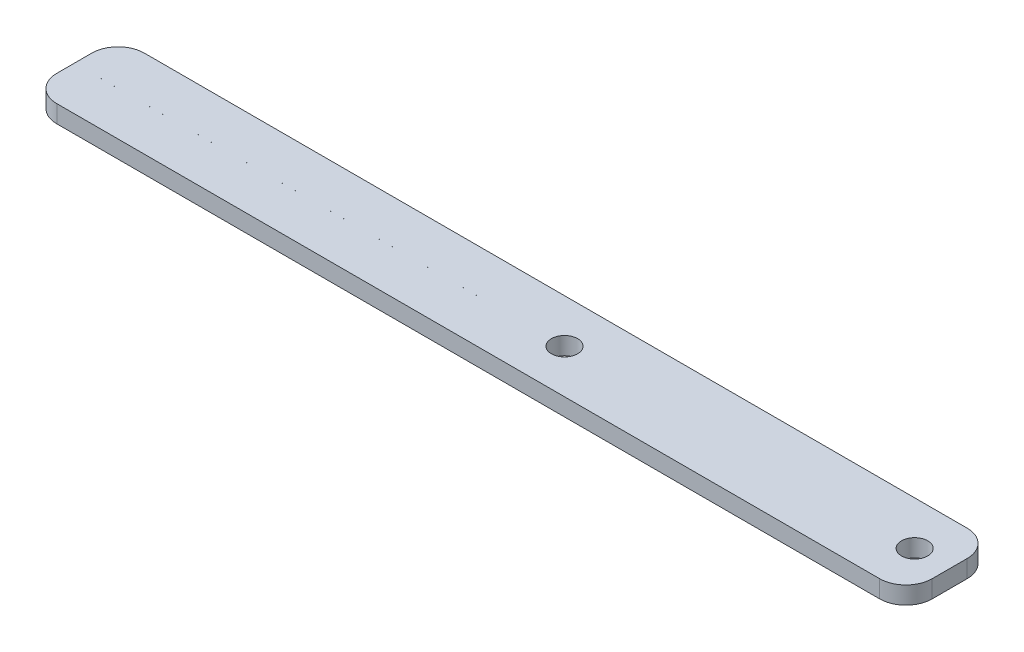
SolidWorks part; units mm, degrees
ref_plane "Front Plane" through (0, 0, 0) normal (0, 0, 1) x (1, 0, 0)
ref_plane "Top Plane" through (0, 0, 0) normal (0, 1, 0) x (1, 0, 0)
ref_plane "Right Plane" through (0, 0, 0) normal (1, 0, 0) x (0, 0, -1)
sketch "Sketch1" plane through (0, 0, 0) normal (0, 1, 0) x (1, 0, 0)
  line L1 (-50, 5) -> (50, 5)
  line L2 (-50, 5) -> (-50, -5)
  line L3 (-50, -5) -> (50, -5)
  line L4 (50, 5) -> (50, -5)
  line L5 (-50, 5) -> (50, -5) construction
  line L6 (-50, -5) -> (50, 5) construction
  point P0 (0, 0)
  dimension "D1" = 10
  dimension "D2" = 100
extrude "Boss-Extrude1" add sketch "Sketch1" along normal blind 2
sketch "Sketch2" plane through (0, 2, 0) normal (0, 1, 0) x (1, 0, 0)
  line L0 (26.3156, 5) -> (26.3156, -5) construction
  line L1 (-50, -5) -> (50, -5) construction
  line L2 (-50, 5) -> (-50, -5) construction
  line L4 (-3, 0.0005) -> (-50, 0.0005)
  line L5 (-3, 0.0005) -> (-3, -0.0005)
  line L6 (-3, -0.0005) -> (-50, -0.0005)
  line L7 (-50, 0.0005) -> (-50, -0.0005)
  line L8 (-3, 0.0005) -> (-50, -0.0005) construction
  line L9 (-3, -0.0005) -> (-50, 0.0005) construction
  point P0 (-26.5, 0)
  point P10 (26.3156, 0)
  point P14 (-50, 0)
  dimension "D1" = 47
  dimension "D2" = 0.001
fillet "Fillet1" radius 3 4 edges at (50, 1, 5) (50, 1, -5) (-50, 1, -5) (-50, 1, 5)
hole_wizard "Ø3.0mm Dowel Hole1" positions "Sketch3" profile "Sketch5" hole size "Ø3.0" standard "ISO" end condition through all
sketch "Sketch3" plane through (0, 2, 0) normal (0, 1, 0) x (1, 0, 0)
  line L0 (50, -2) -> (50, 2) construction
  point P0 (46, 0)
  point P5 (6, 0)
  dimension "D1" = 40
  dimension "D2" = 4
sketch "Sketch5" plane through (46, 2, 0) normal (1, 0, 0) x (0, 0, 1)
  line L0 (0, 0) -> (0, 2)
  line L1 (0, 2) -> (1.5, 2)
  line L2 (1.5, 2) -> (1.5, 0)
  line L5 (1.5, 0) -> (0, 0)
  line L11 (0, -22.0399) -> (0, 107.95) construction
  dimension "Thru Hole Dia." = 3
  dimension "Thru Hole Depth" = 2
extrude "Cut-Extrude1" cut sketch "Sketch2" against normal blind 10
